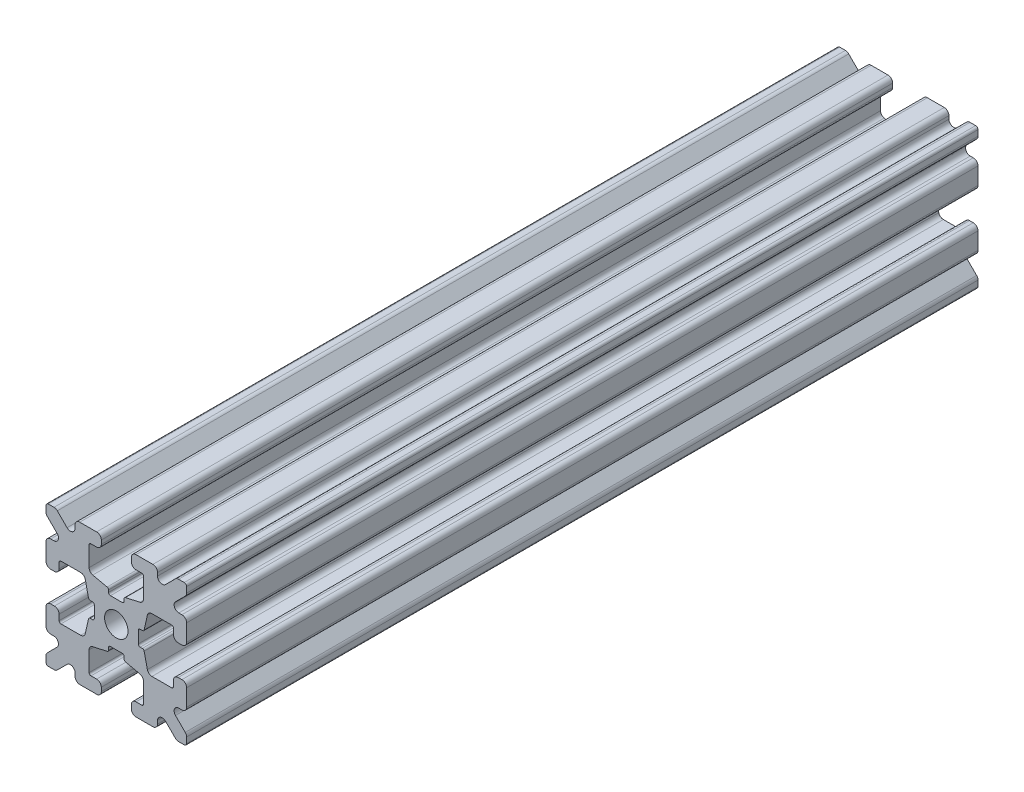
SolidWorks part; units mm, degrees
ref_plane "Front Plane" through (0, 0, 0) normal (0, 0, 1) x (1, 0, 0)
ref_plane "Top Plane" through (0, 0, 0) normal (0, 1, 0) x (1, 0, 0)
ref_plane "Right Plane" through (0, 0, 0) normal (1, 0, 0) x (0, 0, -1)
sketch "Sketch1" plane through (0, 0, 0) normal (0, 0, 1) x (1, 0, 0)
  line L1 (-7.5, -7.5) -> (7.5, -7.5)
  line L2 (-7.5, -7.5) -> (-7.5, 7.5)
  line L3 (-7.5, 7.5) -> (7.5, 7.5)
  line L4 (7.5, -7.5) -> (7.5, 7.5)
  line L5 (-7.5, -7.5) -> (7.5, 7.5) construction
  line L6 (-7.5, 7.5) -> (7.5, -7.5) construction
  circle A0 centre (0, 0) radius 1.25
  point P0 (0, 0)
  dimension "D2" = 2.5
  dimension "D1" = 15
extrude "Boss-Extrude1" add sketch "Sketch1" along normal mid plane 84.428
fillet "Fillet1" radius 0.25 4 edges at (7.5, -7.5, 0) (-7.5, -7.5, 0) (7.5, 7.5, 0) (-7.5, 7.5, 0)
sketch "Sketch2" plane through (0, 0, 42.214) normal (0, 0, 1) x (1, 0, 0)
  line L0 (-7.5, 7.25) -> (-7.5, -7.25) construction
  line L1 (-7.5, 1.6) -> (-6.1, 1.6)
  line L2 (-7.5, 1.6) -> (-7.5, -1.6)
  line L3 (-7.5, -1.6) -> (-6.1, -1.6)
  line L4 (-6.1, 1.6) -> (-6.1, 2.9)
  line L5 (0, 0) -> (-12.1036, 0) construction
  line L6 (-6.1, -2.9) -> (-3.4, -2.9)
  line L7 (0, 0) -> (-7.25, 7.25) construction
  line L8 (-6.1, 2.9) -> (-3.4, 2.9)
  line L9 (-3.4, -2.9) -> (-3.4, 2.9)
  line L10 (55, 0) -> (-55, 0) construction
  line L11 (-6.1, -2.9) -> (-6.1, -1.6)
  line L12 (2.9, 6.1) -> (1.6, 6.1)
  line L13 (2.9, 3.4) -> (-2.9, 3.4)
  line L14 (-2.9, 6.1) -> (-2.9, 3.4)
  line L15 (2.9, 6.1) -> (2.9, 3.4)
  line L16 (-1.6, 6.1) -> (-2.9, 6.1)
  line L17 (1.6, 7.5) -> (1.6, 6.1)
  line L18 (-1.6, 7.5) -> (1.6, 7.5)
  line L19 (-1.6, 7.5) -> (-1.6, 6.1)
  line L20 (-1.6, -7.5) -> (-1.6, -6.1)
  line L21 (-1.6, -7.5) -> (1.6, -7.5)
  line L22 (1.6, -7.5) -> (1.6, -6.1)
  line L23 (-1.6, -6.1) -> (-2.9, -6.1)
  line L24 (2.9, -6.1) -> (2.9, -3.4)
  line L25 (-2.9, -6.1) -> (-2.9, -3.4)
  line L26 (2.9, -3.4) -> (-2.9, -3.4)
  line L27 (2.9, -6.1) -> (1.6, -6.1)
  line L28 (6.1, -2.9) -> (6.1, -1.6)
  line L29 (3.4, -2.9) -> (3.4, 2.9)
  line L30 (6.1, 2.9) -> (3.4, 2.9)
  line L31 (6.1, -2.9) -> (3.4, -2.9)
  line L32 (6.1, 1.6) -> (6.1, 2.9)
  line L33 (7.5, -1.6) -> (6.1, -1.6)
  line L34 (7.5, 1.6) -> (7.5, -1.6)
  line L35 (7.5, 1.6) -> (6.1, 1.6)
  dimension "D1" = 3.2
  dimension "D2" = 5.8
  dimension "D3" = 1.4
  dimension "D4" = 2.7
extrude "Cut-Extrude1" cut sketch "Sketch2" against normal through all
sketch "Sketch4" plane through (0, 0, 42.214) normal (0, 0, 1) x (1, 0, 0)
  line L0 (-3.4, 2.9) -> (-2.75, 0)
  line L1 (55, 0) -> (-55, 0) construction
  line L2 (-2.75, 0) -> (-3.4, -2.9)
  line L3 (-3.4, -2.9) -> (-3.4, 2.9) construction
  line L4 (-3.4, 2.9) -> (-3.4, -2.9)
  line L5 (-2.9, 3.4) -> (0, 2.75)
  line L6 (0, 2.75) -> (2.9, 3.4)
  line L7 (2.9, 3.4) -> (-2.9, 3.4)
  line L8 (3.4, 2.9) -> (2.75, 0)
  line L9 (2.75, 0) -> (3.4, -2.9)
  line L10 (3.4, -2.9) -> (3.4, 2.9)
  line L11 (-2.9, -3.4) -> (0, -2.75)
  line L12 (0, -2.75) -> (2.9, -3.4)
  line L13 (2.9, -3.4) -> (-2.9, -3.4)
  circle A2 centre (0, 0) radius 2.75
  circle A3 centre (0, 0) radius 2.75 construction
  dimension "D1" = 1.5
extrude "Cut-Extrude3" cut sketch "Sketch4" against normal through all
fillet "Fillet3" radius 0.5 16 edges at (-6.1, -1.6, 0) (-7.5, -1.6, 0) (-6.1, 1.6, 0) (-7.5, 1.6, 0) (-1.6, -7.5, 0) (-1.6, -6.1, 0) (1.6, -7.5, 0) (1.6, -6.1, 0) (6.1, -1.6, 0) (7.5, -1.6, 0) (7.5, 1.6, 0) (6.1, 1.6, 0) (1.6, 7.5, 0) (1.6, 6.1, 0) (-1.6, 7.5, 0) (-1.6, 6.1, 0)
fillet "Fillet4" radius 0.5 8 edges at (-3.4, 2.9, 0) (-3.4, -2.9, 0) (2.9, -3.4, 0) (-2.9, -3.4, 0) (3.4, -2.9, 0) (3.4, 2.9, 0) (-2.9, 3.4, 0) (2.9, 3.4, 0)
fillet "Fillet5" radius 3 4 edges at (0, -2.75, 0) (2.75, 0, 0) (-2.75, 0, 0) (0, 2.75, 0)
fillet "Fillet6" radius 0.2 8 edges at (-2.9, -6.1, 0) (2.9, -6.1, 0) (6.1, -2.9, 0) (6.1, 2.9, 0) (2.9, 6.1, 0) (-2.9, 6.1, 0) (-6.1, -2.9, 0) (-6.1, 2.9, 0)
sketch "Sketch5" plane through (0, 0, 42.214) normal (0, 0, 1) x (1, 0, 0)
  line L0 (0, 0) -> (-7.25, 7.25) construction
  line L1 (-7.5, 6.4393) -> (-5.4607, 4.4)
  line L2 (-6.4393, 7.5) -> (-4.4, 5.4607)
  line L3 (-7.5, 4.4) -> (-5.4607, 4.4)
  line L4 (-3.8003, 2.9) -> (-5.9, 2.9) construction
  line L5 (0, 0) -> (-12.1819, 0) construction
  line L6 (-4.4, 7.5) -> (-4.4, 5.4607)
  line L7 (-2.9, 5.9) -> (-2.9, 3.8003) construction
  line L8 (-7.5, 6.4393) -> (-7.5, 4.4)
  line L9 (-7.5, 7.25) -> (-7.5, 2.1) construction
  line L10 (2.1, -7.5) -> (7.25, -7.5) construction
  line L11 (7.5, -7.25) -> (7.5, -2.1) construction
  line L12 (7.25, 7.5) -> (2.1, 7.5) construction
  line L13 (-2.1, 7.5) -> (-7.25, 7.5) construction
  line L14 (-4.4, 7.5) -> (-6.4393, 7.5)
  line L16 (55, 0) -> (-55, 0) construction
  line L17 (0, 0) -> (0, 10.993) construction
  line L18 (0, -54.6431) -> (0, 54.6431) construction
  line L20 (4.4, 7.5) -> (6.4393, 7.5)
  line L22 (7.5, 6.4393) -> (7.5, 4.4)
  line L23 (4.4, 7.5) -> (4.4, 5.4607)
  line L24 (7.5, 4.4) -> (5.4607, 4.4)
  line L25 (6.4393, 7.5) -> (4.4, 5.4607)
  line L26 (7.5, 6.4393) -> (5.4607, 4.4)
  line L27 (7.5, -6.4393) -> (5.4607, -4.4)
  line L28 (6.4393, -7.5) -> (4.4, -5.4607)
  line L29 (7.5, -4.4) -> (5.4607, -4.4)
  line L30 (4.4, -7.5) -> (4.4, -5.4607)
  line L31 (7.5, -6.4393) -> (7.5, -4.4)
  line L33 (4.4, -7.5) -> (6.4393, -7.5)
  line L36 (-4.4, -7.5) -> (-6.4393, -7.5)
  line L38 (-7.5, -6.4393) -> (-7.5, -4.4)
  line L39 (-4.4, -7.5) -> (-4.4, -5.4607)
  line L40 (-7.5, -4.4) -> (-5.4607, -4.4)
  line L41 (-6.4393, -7.5) -> (-4.4, -5.4607)
  line L42 (-7.5, -6.4393) -> (-5.4607, -4.4)
  dimension "D1" = 1.5
  dimension "D2" = 1.5
  dimension "D3" = 1.5
extrude "Cut-Extrude4" cut sketch "Sketch5" against normal through all
fillet "Fillet8" radius 0.5 24 edges at (-5.4607, 4.4, 0) (-7.5, 4.4, 0) (-5.4607, -4.4, 0) (-7.5, -4.4, 0) (-4.4, -7.5, 0) (-4.4, -5.4607, 0) (4.4, -7.5, 0) (4.4, -5.4607, 0) (5.4607, -4.4, 0) (7.5, -4.4, 0) (7.5, 4.4, 0) (5.4607, 4.4, 0) (4.4, 5.4607, 0) (4.4, 7.5, 0) (-4.4, 5.4607, 0) (-4.4, 7.5, 0) (-6.4393, 7.5, 0) (-7.5, 6.4393, 0) (6.4393, 7.5, 0) (7.5, 6.4393, 0) (6.4393, -7.5, 0) (7.5, -6.4393, 0) (-6.4393, -7.5, 0) (-7.5, -6.4393, 0)
sketch "Sketch6" plane through (0, 0, 42.214) normal (0, 0, 1) x (1, 0, 0)
  line L0 (0, 0) -> (0, 11.013) construction
  line L1 (0.6561, 2.8971) -> (2.1235, 2.8971) construction
  line L2 (0, -54.6431) -> (0, 54.6431) construction
  line L3 (0, 0) -> (7.25, 7.25) construction
  line L4 (7.5, 0.8255) -> (7.5, -0.8255)
  line L5 (2.3471, 0.8255) -> (7.5, 0.8255)
  line L6 (0, 0) -> (12.4016, 0) construction
  line L7 (0.8255, -7.5) -> (-0.8255, -7.5)
  line L8 (2.3471, -0.8255) -> (2.3471, 0.8255)
  line L9 (0.8255, -2.3471) -> (0.8255, -7.5)
  line L10 (7.5, -0.8255) -> (2.3471, -0.8255)
  line L11 (-7.5, -0.8255) -> (-2.3471, -0.8255)
  line L12 (-2.3471, -0.8255) -> (-2.3471, 0.8255)
  line L13 (-0.8255, -2.3471) -> (0.8255, -2.3471)
  line L14 (-0.8255, 7.5) -> (-0.8255, 2.3471)
  line L15 (-0.8255, 2.3471) -> (0.8255, 2.3471)
  line L16 (-0.8255, -7.5) -> (-0.8255, -2.3471)
  line L17 (0.8255, 2.3471) -> (0.8255, 7.5)
  line L18 (0.8255, 7.5) -> (-0.8255, 7.5)
  line L19 (3.9, 7.5) -> (2.1, 7.5) construction
  line L20 (-2.3471, 0.8255) -> (-7.5, 0.8255)
  line L21 (-7.5, 0.8255) -> (-7.5, -0.8255)
  point P5 (0, -2.5973)
  point P7 (0, 2.5973)
  dimension "D3" = 0.55
  dimension "D1" = 1.651
extrude "Cut-Extrude5" cut sketch "Sketch6" against normal through all
fillet "Fillet10" radius 0.2 16 edges at (-2.935, 0.8255, 0) (-2.935, -0.8255, 0) (2.935, -0.8255, 0) (2.935, 0.8255, 0) (0.8255, 2.935, 0) (-0.8255, 2.935, 0) (-2.3471, 0.8255, 0) (-2.3471, -0.8255, 0) (0.8255, 2.3471, 0) (-0.8255, 2.3471, 0) (2.3471, 0.8255, 0) (2.3471, -0.8255, 0) (0.8255, -2.935, 0) (0.8255, -2.3471, 0) (-0.8255, -2.3471, 0) (-0.8255, -2.935, 0)
